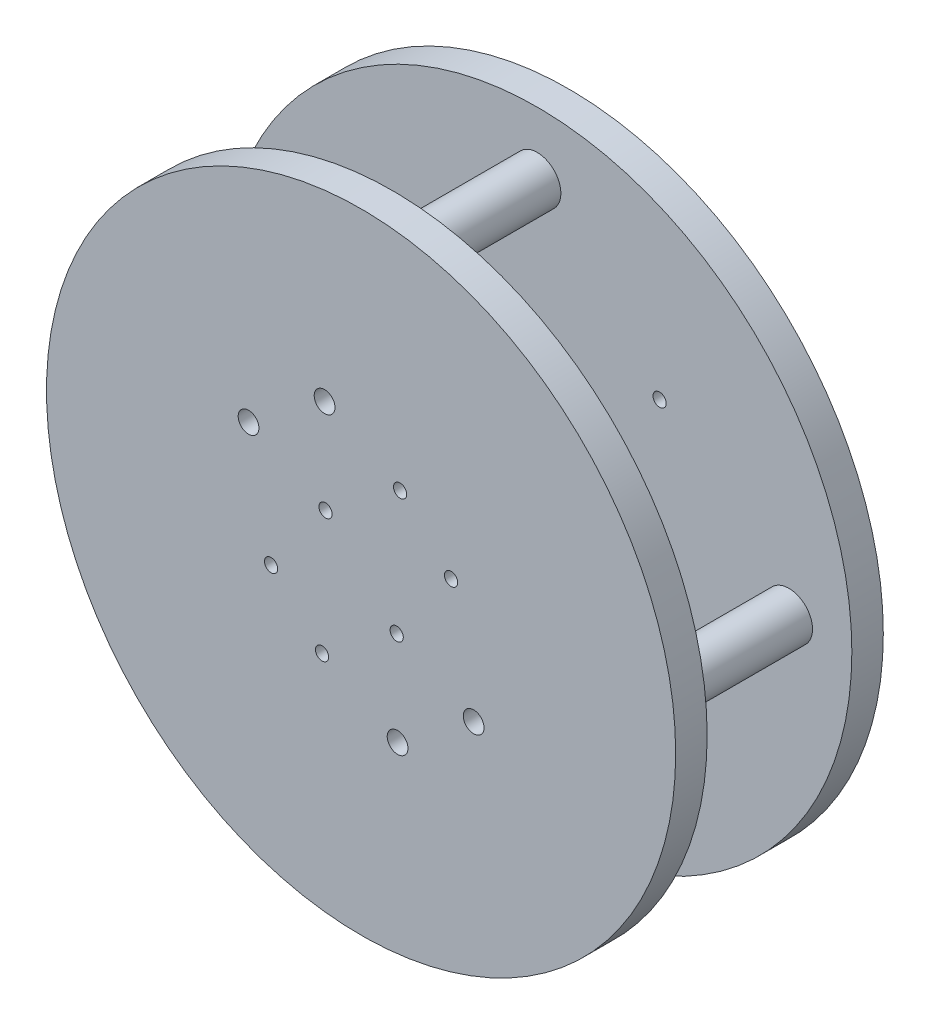
SolidWorks part; units mm, degrees
ref_plane "前视基准面" through (0, 0, 0) normal (0, 0, 1) x (1, 0, 0)
ref_plane "上视基准面" through (0, 0, 0) normal (0, 1, 0) x (1, 0, 0)
ref_plane "右视基准面" through (0, 0, 0) normal (1, 0, 0) x (0, 0, -1)
sketch "草图1" plane through (0, 0, 0) normal (0, 0, 1) x (1, 0, 0)
  line L0 (0, 0) -> (0, -138.3959) construction
  line L1 (0, 0) -> (120.3166, 0) construction
  circle A0 centre (0, 0) radius 100
  circle A2 centre (0, 0) radius 100
  circle A4 centre (0, 0) radius 100
  circle A6 centre (0, 0) radius 100
  circle A8 centre (0, 0) radius 100
  circle A10 centre (0, 0) radius 100
  dimension "D1" = 200
  dimension "D4" = 6
extrude "凸台-拉伸1" add sketch "草图1" along normal blind 10 contours A0
sketch "草图12" plane through (0, 0, 10) normal (0, 0, 1) x (1, 0, 0)
  circle A0 centre (-80, 0) radius 7.5
  circle A1 centre (0, 80) radius 7.5
  circle A2 centre (80, 0) radius 7.5
  circle A3 centre (0, -80) radius 7.5
  point P12 (0, 0)
  dimension "D1" = 15
  dimension "D2" = 80
  dimension "D3" = 4
extrude "凸台-拉伸3" add sketch "草图12" along normal blind 46
sketch "草图14" plane through (0, 0, 56) normal (0, 0, 1) x (1, 0, 0)
  circle A0 centre (0, 0) radius 100
extrude "凸台-拉伸4" add sketch "草图14" along normal blind 10
sketch "草图15" plane through (0, 0, 66) normal (0, 0, 1) x (1, 0, 0)
  line L0 (-100, 0) -> (0, 100) construction
  line L1 (0, 100) -> (100, 0) construction
  line L2 (100, 0) -> (0, -100) construction
  line L3 (0, -100) -> (-100, 0) construction
  line L4 (-50, 50) -> (50, -50) construction
  line L5 (12.4027, 28.6095) -> (63.2455, -22.2333) construction
  line L6 (0, 0) -> (50, 50) construction
  circle A0 centre (0, 0) radius 100 construction
  circle A1 centre (-11.3137, 11.3137) radius 2.1
  circle A2 centre (11.3137, -11.3137) radius 2.1
  circle A3 centre (12.4027, 28.6095) radius 2.1
  circle A5 centre (28.6095, 12.4027) radius 2.1
  circle A6 centre (-12.4027, -28.6095) radius 2.1
  circle A7 centre (-28.6095, -12.4027) radius 2.1
  dimension "D1" = 4.2
  dimension "D2" = 4.2
  dimension "D5" = 4.2
  dimension "D3" = 16
  dimension "D4" = 16
  dimension "D6" = 29
  dimension "D7" = 11.46
extrude "切除-拉伸7" cut sketch "草图15" against normal blind 10 contours A1 | A2
extrude "切除-拉伸8" cut sketch "草图15<3>" against normal through all contours A7 | A6 | A3 | A5
sketch "草图15<3>" plane through (0, 0, 66) normal (0, 0, 1) x (1, 0, 0) same geometry as "草图15"
sketch "草图18" plane through (0, 0, 66) normal (0, 0, 1) x (1, 0, 0)
  circle A0 centre (-11.6012, 41.1146) radius 3.3
  circle A1 centre (-35.7749, 23.3486) radius 3.3
  circle A2 centre (11.6012, -41.1146) radius 3.3
  circle A3 centre (35.7749, -23.3486) radius 3.3
extrude "切除-拉伸9" cut sketch "草图18" against normal blind 5
sketch "草图20" plane through (0, 0, 0) normal (0, 0, -1) x (-1, 0, 0)
  line L0 (-119.8075, 0) -> (154.4372, 0) construction
  line L1 (0, 108.2177) -> (0, -107.3799) construction
  line L2 (0, 0) -> (92.6067, 92.6067) construction
  circle A0 centre (0, 0) radius 55 construction
  circle A1 centre (38.8909, 38.8909) radius 6.2262
  circle A3 centre (0, 0) radius 100
  circle A4 centre (0, 0) radius 100
  point P10 (0, 0)
  dimension "D1" = 110
  dimension "D3" = 0
  dimension "D2" = 45
sketch "草图21" plane through (0, 0, 10) normal (0, 0, 1) x (1, 0, 0)
  circle A0 centre (-38.8909, 38.8909) radius 6.2262 construction
  circle A1 centre (-38.8909, 38.8909) radius 6.2262
hole_wizard "M5 螺纹孔1" positions "3D草图1" profile "草图22" tap size "M5" standard "GB" end condition up to next
sketch3d "3D草图1"
  point P0 (-38.8909, 38.8909, 10)
sketch "草图22" plane through (-38.8909, 38.8909, 10) normal (1, 0, 0) x (0, -1, 0)
  line L0 (0, 0) -> (0, 10)
  line L1 (0, 10) -> (2.1, 10)
  line L2 (2.1, 10) -> (2.1, 0)
  line L5 (2.1, 0) -> (0, 0)
  line L11 (0, -6.35) -> (0, 107.95) construction
  dimension "通孔螺纹孔钻头直径" = 4.2
  dimension "通孔螺纹孔钻头深度" = 10
pattern_circular "阵列(圆周)1" count 4 over 360 about axis through (0, 0, 0) along (0, 0, 1) of "M5 螺纹孔1"
